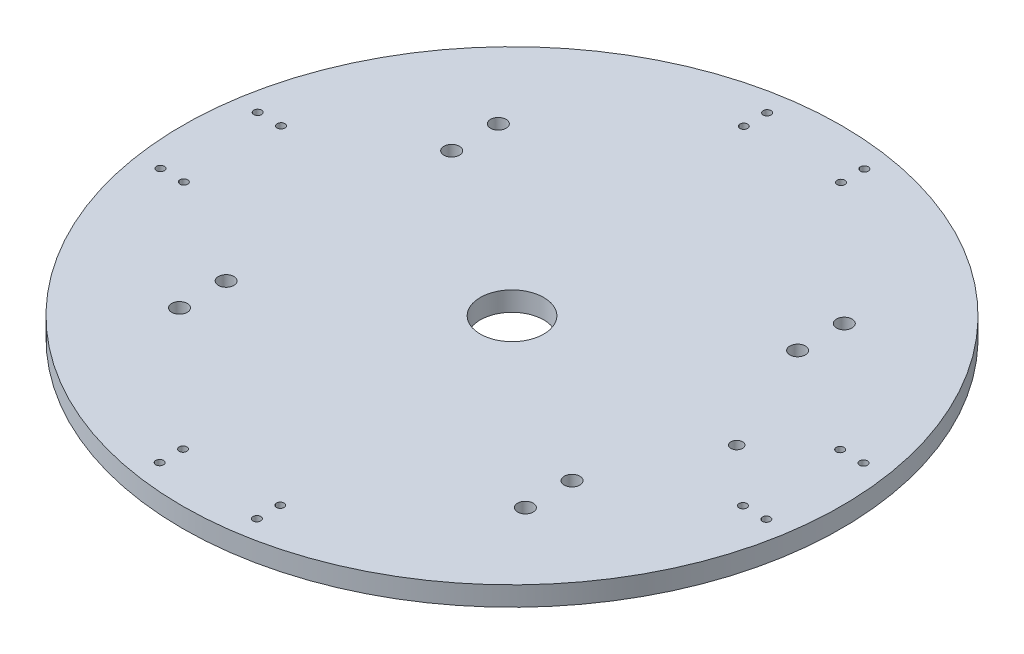
SolidWorks part; units mm, degrees
material "ABS"
ref_plane "Front Plane" through (0, 0, 0) normal (0, 0, 1) x (1, 0, 0)
ref_plane "Top Plane" through (0, 0, 0) normal (0, 1, 0) x (1, 0, 0)
ref_plane "Right Plane" through (0, 0, 0) normal (1, 0, 0) x (0, 0, -1)
sketch "Sketch2" plane through (0, 0, 0) normal (0, 1, 0) x (1, 0, 0)
  line L1 (0, 0) -> (200, 0)
  line L2 (0, 0) -> (0, 200)
  line L3 (0, 200) -> (200, 200)
  line L4 (200, 0) -> (200, 200)
  dimension "D1" = 200
  dimension "D2" = 200
extrude "Boss-Extrude2" add sketch "Sketch2" along normal blind 60
sketch "Sketch3" plane through (0, 0, 0) normal (0, 0, 1) x (1, 0, 0)
  line L0 (40, 60) -> (80.9808, 130.9808)
  line L1 (0, 60) -> (200, 60) construction
  line L2 (160, 60) -> (119.0192, 130.9808)
  line L3 (40, 60) -> (160, 60)
  arc A0 (80.9808, 130.9808) -> (119.0192, 130.9808) centre (100, 120) cw
  dimension "D1" = 120
  dimension "D2" = 40
  dimension "D3" = 60
  dimension "D4" = 60
  dimension "D5" = 60
extrude "Boss-Extrude3" add sketch "Sketch3" against normal blind 41 from offset 38 offset against normal yes
sketch "Sketch4" plane through (0, 0, -79) normal (0, 0, -1) x (-1, 0, 0)
  line L0 (-106.5, 103) -> (-93.5, 103)
  line L1 (-106.5, 107) -> (-93.5, 107)
  line L2 (-103.5, 107) -> (-102, 122)
  line L3 (-96.5, 107) -> (-98, 122)
  line L4 (-106.5, 105) -> (-93.5, 105) construction
  line L5 (-103, 103) -> (-102, 91)
  line L6 (-97, 103) -> (-98, 91)
  line L8 (-40, 60) -> (-160, 60) construction
  arc A0 (-106.5, 103) -> (-106.5, 107) centre (-106.5, 105) cw
  arc A1 (-93.5, 107) -> (-93.5, 103) centre (-93.5, 105) cw
  arc A2 (-102, 122) -> (-98, 122) centre (-100, 122) cw
  arc A3 (-102, 91) -> (-98, 91) centre (-100, 91) ccw
  point P6 (-108.5, 105)
  point P7 (-91.5, 105)
  point P12 (-100, 107)
  point P14 (-100, 124)
  point P19 (-100, 103)
  point P21 (-100, 89)
  point P30 (-100, 105)
  dimension "D3" = 2
  dimension "D1" = 17
  dimension "D2" = 7
  dimension "D4" = 3.5
  dimension "D5" = 17
  dimension "D6" = 6
  dimension "D7" = 3
  dimension "D8" = 14
  dimension "D9" = 4
  dimension "D10" = 4
  dimension "D11" = 60
  dimension "D12" = 45
sketch "Sketch5" plane through (0, 0, 0) normal (0, -1, 0) x (1, 0, 0)
  line L0 (0, 0) -> (200, 0) construction
  line L1 (10, -10) -> (190, -10)
  line L2 (10, -10) -> (10, -190)
  line L3 (10, -190) -> (190, -190)
  line L4 (190, -10) -> (190, -190)
  line L5 (0, -200) -> (0, 0) construction
  line L6 (200, -200) -> (0, -200) construction
  line L7 (200, 0) -> (200, -200) construction
  dimension "D1" = 10
  dimension "D2" = 10
  dimension "D3" = 10
  dimension "D4" = 10
extrude "Cut-Extrude2" cut sketch "Sketch5" against normal blind 50
sketch "Sketch7" plane through (0, 0, -200) normal (0, 0, -1) x (-1, 0, 0)
  line L0 (-160, 60) -> (-40, 60)
  line L1 (-40, 60) -> (-80.9808, 130.9808)
  line L2 (-160, 60) -> (-119.0192, 130.9808)
  arc A0 (-119.0192, 130.9808) -> (-80.9808, 130.9808) centre (-100, 120) cw
extrude "Boss-Extrude4" add sketch "Sketch7" against normal blind 30 from offset 51.2 offset against normal yes
sketch "Sketch8" plane through (0, 0, -38) normal (0, 0, 1) x (1, 0, 0)
  line L9 (48.6603, 65) -> (151.3397, 65)
  line L10 (85.3109, 128.4808) -> (48.6603, 65)
  line L11 (151.3397, 65) -> (114.6891, 128.4808)
  line L12 (48.6603, 65) -> (151.3397, 65)
  line L13 (85.3109, 128.4808) -> (48.6603, 65)
  line L16 (151.3397, 65) -> (114.6891, 128.4808)
  arc A6 (114.6891, 128.4808) -> (85.3109, 128.4808) centre (100, 120) ccw
  arc A7 (114.6891, 128.4808) -> (85.3109, 128.4808) centre (100, 120) ccw
  dimension "D1" = 5
extrude "Cut-Extrude3" cut sketch "Sketch8" against normal blind 35
sketch "Sketch9" plane through (0, 0, -118.8) normal (0, 0, 1) x (1, 0, 0)
  line L0 (200, 60) -> (0, 60) construction
  line L1 (95, 105) -> (95, 149.6169)
  line L2 (105, 105) -> (105, 149.6169)
  line L3 (95, 149.6169) -> (105, 149.6169)
  circle A0 centre (100, 105) radius 5
  arc M3 (119.0192, 130.9808) -> (80.9808, 130.9808) centre (100, 120) ccw
  dimension "D1" = 10
  dimension "D2" = 60
  dimension "D3" = 45
extrude "Cut-Extrude4" cut sketch "Sketch9" against normal blind 10 contours A0 L2 L1 M3 | A0 region at (100, 125.3301, -118.8) region at (100, 105, -118.8)
sketch "Sketch10" plane through (0, 0, -148.8) normal (0, 0, -1) x (-1, 0, 0)
  line L12 (-200, 60) -> (0, 60) construction
  line L13 (-119.0192, 130.9808) -> (-160, 60) construction
  line L14 (-40, 60) -> (-80.9808, 130.9808) construction
  line L15 (-160, 60) -> (-40, 60)
  line L16 (-119.0192, 130.9808) -> (-160, 60)
  line L17 (-40, 60) -> (-80.9808, 130.9808)
  line L18 (-95, 105) -> (-95, 149.6169) construction
  line L19 (-105, 105) -> (-105, 149.6169) construction
  line L20 (-95, 105) -> (-95, 141.3848)
  line L21 (-105, 105) -> (-105, 141.3848)
  line L22 (-151.3397, 65) -> (-48.6603, 65)
  line L23 (-48.6603, 65) -> (-85.3109, 128.4808)
  line L24 (-90, 105) -> (-90, 133.7001)
  line L25 (-110, 105) -> (-110, 133.7001)
  line L26 (-114.6891, 128.4808) -> (-151.3397, 65)
  arc A1 (-80.9808, 130.9808) -> (-119.0192, 130.9808) centre (-100, 120) ccw construction
  arc A2 (-80.9808, 130.9808) -> (-95, 141.3848) centre (-100, 120) ccw
  circle A3 centre (-100, 105) radius 5 construction
  arc A4 (-105, 105) -> (-95, 105) centre (-100, 105) ccw
  arc A5 (-105, 141.3848) -> (-119.0192, 130.9808) centre (-100, 120) ccw
  arc A6 (-85.3109, 128.4808) -> (-90, 133.7001) centre (-100, 120) ccw
  arc A7 (-110, 105) -> (-90, 105) centre (-100, 105) ccw
  arc A8 (-110, 133.7001) -> (-114.6891, 128.4808) centre (-100, 120) ccw
  point P14 (-105, 141.3848)
  point P15 (-95, 141.3848)
  dimension "D1" = 5
extrude "Cut-Extrude6" cut sketch "Sketch10" against normal blind 26 contours L25 A8 L26 L22 L23 A6 L24 A7 region at (100, 87.3602, -148.8)
sketch "Sketch11" plane through (0, 60, 0) normal (0, 1, 0) x (1, 0, 0)
  line L1 (40, 118.8) -> (160, 118.8)
  line L2 (40, 118.8) -> (40, 108.8)
  line L3 (40, 108.8) -> (160, 108.8)
  line L4 (160, 118.8) -> (160, 108.8)
  dimension "D1" = 120
  dimension "D2" = 10
extrude "Cut-Extrude7" cut sketch "Sketch11" against normal blind 26
sketch "Sketch12" plane through (200, 0, 0) normal (1, 0, 0) x (0, 0, -1)
  line L0 (0, 60) -> (200, 60) construction
  line L1 (10, 0) -> (190, 0)
  line L2 (10, 0) -> (10, 50)
  line L3 (10, 50) -> (190, 50)
  line L4 (190, 0) -> (190, 50)
  dimension "D1" = 10
  dimension "D2" = 10
extrude "Cut-Extrude8" cut sketch "Sketch12" against normal blind 200
sketch "Sketch13" plane through (0, 0, 0) normal (0, 0, 1) x (1, 0, 0)
  line L0 (0, 0) -> (200, 0) construction
  line L1 (10, 0) -> (190, 0)
  line L2 (10, 0) -> (10, 50)
  line L3 (10, 50) -> (190, 50)
  line L4 (190, 0) -> (190, 50)
  line L5 (200, 60) -> (200, 0) construction
  line L6 (0, 60) -> (200, 60) construction
  dimension "D1" = 10
  dimension "D2" = 10
  dimension "D3" = 10
extrude "Cut-Extrude9" cut sketch "Sketch13" against normal blind 200
sketch "Sketch15" plane through (0, 0, -73) normal (0, 0, 1) x (1, 0, 0)
  line L0 (106.5, 105) -> (93.5, 105) construction
  line L2 (90.1, 74.4) -> (109.9, 74.4)
  line L3 (90.1, 74.4) -> (90.1, 115)
  line L4 (90.1, 115) -> (109.9, 115)
  line L5 (109.9, 74.4) -> (109.9, 115)
  circle A0 centre (100, 105) radius 4.0162
  point P8 (100, 74.4)
  dimension "D1" = 40.6
  dimension "D2" = 19.8
  dimension "D3" = 10
extrude "Cut-Extrude11" cut sketch "Sketch15" against normal blind 10 contours A0 | L2 L5 L4 L3 A0 region at (100, 94.0071, -73) region at (100, 105, -73)
sketch "Sketch16" plane through (0, 0, -73) normal (0, 0, 1) x (1, 0, 0)
  line L3 (109.9, 74.4) -> (109.9, 115) construction
  line L4 (90.1, 74.4) -> (109.9, 74.4) construction
  line L5 (90.1, 74.4) -> (90.1, 115) construction
  line L6 (88.1, 115) -> (88.1, 72.4)
  line L7 (88.1, 72.4) -> (111.9, 72.4)
  line L8 (111.9, 72.4) -> (111.9, 115)
  line L9 (88.1, 115) -> (88.1, 72.4)
  line L10 (88.1, 72.4) -> (111.9, 72.4)
  line L11 (111.9, 72.4) -> (111.9, 115)
  line L12 (109.9, 74.4) -> (109.9, 115)
  line L13 (90.1, 74.4) -> (109.9, 74.4)
  line L14 (90.1, 74.4) -> (90.1, 115)
  line L15 (88.1, 115) -> (90.1, 115)
  line L16 (109.9, 115) -> (111.9, 115)
  dimension "D1" = 2
extrude "Boss-Extrude5" add sketch "Sketch16" along normal blind 26
sketch "Sketch20" plane through (0, 0, -79) normal (0, 0, -1) x (-1, 0, 0)
  line L0 (-90.1, 74.4) -> (-90.1, 115) construction
  line L1 (-109.9, 115) -> (-90.1, 115)
  line L2 (-109.9, 115) -> (-109.9, 122)
  line L3 (-109.9, 122) -> (-90.1, 122)
  line L4 (-90.1, 115) -> (-90.1, 122)
  line L6 (-109.9, 74.4) -> (-90.1, 74.4)
  line L7 (-109.9, 74.4) -> (-109.9, 67.4)
  line L8 (-109.9, 67.4) -> (-90.1, 67.4)
  line L9 (-90.1, 74.4) -> (-90.1, 67.4)
  dimension "D1" = 7
  dimension "D2" = 7
extrude "Cut-Extrude14" cut sketch "Sketch20" against normal blind 8.2
sketch "Sketch22" plane through (4.0192, -2.3205, 0) normal (-0.866, 0.5, 0) x (0, 0, 1)
  line L4 (-144.8, 81.5368) -> (-122.8, 81.5368)
  line L5 (-38, 71.9615) -> (-38, 131.9615) construction
  line L6 (-75, 151.923) -> (-42, 151.923)
  line L7 (-75, 151.923) -> (-75, 81.566)
  line L8 (-122.8, 75.9615) -> (-122.8, 149.923)
  line L9 (-144.8, 75.9615) -> (-122.8, 75.9615)
  line L10 (-144.8, 149.923) -> (-144.8, 75.9615)
  line L11 (-122.8, 149.923) -> (-144.8, 149.923)
  line L12 (-122.8, 81.5368) -> (-122.8, 149.923)
  line L14 (-144.8, 149.923) -> (-144.8, 81.5368)
  line L15 (-122.8, 149.923) -> (-144.8, 149.923)
  line L16 (-75, 81.566) -> (-42, 81.566)
  line L17 (-42, 151.923) -> (-42, 81.566)
  line L18 (-79, 153.923) -> (-79, 71.9615) construction
  line L19 (-79, 153.923) -> (-38, 153.923) construction
  dimension "D2" = 4
  dimension "D3" = 4
  dimension "D4" = 2
  dimension "D1" = 4
extrude "Cut-Extrude16" cut sketch "Sketch22" against normal blind 6
sketch "Sketch23" plane through (0, 0, -38) normal (0, 0, 1) x (1, 0, 0)
  line L3 (43.4641, 62) -> (42.3094, 60)
  line L4 (0, 60) -> (200, 60) construction
  line L6 (156.5359, 62) -> (117.2872, 129.9808)
  line L7 (43.4641, 62) -> (156.5359, 62)
  line L8 (82.7128, 129.9808) -> (43.4641, 62)
  line L9 (156.5359, 62) -> (117.2872, 129.9808)
  line L11 (82.7128, 129.9808) -> (43.4641, 62)
  line L12 (40, 60) -> (160, 60) construction
  line L13 (157.6906, 60) -> (156.5359, 62)
  line L14 (42.3094, 60) -> (36.9518, 60)
  line L15 (36.9518, 60) -> (100, 183.6882)
  line L16 (100, 183.6882) -> (162.6048, 60)
  line L17 (162.6048, 60) -> (157.6906, 60)
  arc A2 (117.2872, 129.9808) -> (82.7128, 129.9808) centre (100, 120) ccw
  arc A3 (117.2872, 129.9808) -> (82.7128, 129.9808) centre (100, 120) ccw
  dimension "D1" = 2
extrude "Cut-Extrude17" cut sketch "Sketch23" against normal blind 150
sketch "Sketch24" plane through (0, 0, -200) normal (0, 0, -1) x (-1, 0, 0)
  line L0 (-200, 0) -> (-190, 0) construction
  line L1 (-195, 0) -> (-5, 0)
  line L2 (-195, 0) -> (-195, 55)
  line L3 (-195, 55) -> (-5, 55)
  line L4 (-5, 0) -> (-5, 55)
  line L5 (-10, 0) -> (0, 0) construction
  line L9 (-190, 50) -> (-10, 50) construction
  dimension "D1" = 5
extrude "Cut-Extrude18" cut sketch "Sketch24" against normal blind 200
sketch "Sketch38" plane through (0, 0, -148.8) normal (0, 0, -1) x (-1, 0, 0)
  line L3 (-110, 133.7001) -> (-107, 135.7639)
  line L4 (-90, 133.7001) -> (-93, 135.7639)
  line L5 (-90, 105) -> (-90, 133.7001) construction
  line L6 (-110, 105) -> (-110, 133.7001) construction
  line L7 (-90, 105) -> (-90, 133.7001)
  line L8 (-110, 105) -> (-110, 133.7001)
  line L11 (-107, 105) -> (-107, 135.7639)
  line L12 (-93, 105) -> (-93, 135.7639)
  arc A5 (-110, 105) -> (-90, 105) centre (-100, 105) ccw construction
  arc A6 (-110, 105) -> (-90, 105) centre (-100, 105) ccw
  arc A7 (-107, 105) -> (-93, 105) centre (-100, 105) ccw
sketch "Sketch41" plane through (0, 60, 0) normal (0, 1, 0) x (1, 0, 0)
  line L1 (0, 200) -> (200, 200)
  line L2 (0, 200) -> (0, 0)
  line L3 (0, 0) -> (200, 0)
  line L4 (200, 200) -> (200, 0)
  line L5 (42.3094, 148.8) -> (157.6906, 148.8)
  line L6 (42.3094, 148.8) -> (42.3094, 38)
  line L7 (42.3094, 38) -> (157.6906, 38)
  line L8 (157.6906, 148.8) -> (157.6906, 38)
extrude "Cut-Extrude25" cut sketch "Sketch41" against normal blind 100
extrude "Cut-Extrude26" cut sketch "Sketch38" against normal blind 26
sketch "Sketch43" plane through (0, 55, 0) normal (0, -1, 0) x (1, 0, 0)
  line L1 (157.6906, -148.8) -> (42.3094, -148.8) construction
  line L2 (42.3094, -38) -> (157.6906, -38) construction
  circle A0 centre (100, -98.8) radius 85
  point P7 (100, -38)
  dimension "D2" = 170
  dimension "D1" = 50
extrude "Boss-Extrude9" add sketch "Sketch43" against normal blind 5
sketch "Sketch45" plane through (0, 0, -38) normal (0, 0, 1) x (1, 0, 0)
  line L0 (42.3094, 60) -> (82.7128, 129.9808) construction
  line L1 (42.3094, 60) -> (82.7128, 129.9808)
  line L2 (157.6906, 60) -> (42.3094, 60) construction
  line L3 (117.2872, 129.9808) -> (157.6906, 60) construction
  line L4 (157.6906, 60) -> (42.3094, 60)
  line L5 (117.2872, 129.9808) -> (157.6906, 60)
  line L6 (151.3397, 65) -> (114.6891, 128.4808) construction
  line L7 (48.6603, 65) -> (151.3397, 65) construction
  line L8 (85.3109, 128.4808) -> (48.6603, 65) construction
  line L9 (151.3397, 65) -> (114.6891, 128.4808)
  line L10 (48.6603, 65) -> (151.3397, 65)
  line L11 (85.3109, 128.4808) -> (48.6603, 65)
  arc A0 (117.2872, 129.9808) -> (82.7128, 129.9808) centre (100, 120) ccw construction
  arc A1 (117.2872, 129.9808) -> (82.7128, 129.9808) centre (100, 120) ccw
  arc A2 (114.6891, 128.4808) -> (85.3109, 128.4808) centre (100, 120) ccw construction
  arc A3 (114.6891, 128.4808) -> (85.3109, 128.4808) centre (100, 120) ccw
extrude "Cut-Extrude27" cut sketch "Sketch45" against normal blind 11
sketch "Sketch46" plane through (0, 0, -49) normal (0, 0, 1) x (1, 0, 0)
  line L0 (81.7128, 128.2487) -> (46.5343, 67.3177)
  line L1 (81.7128, 128.2487) -> (84.2728, 126.7707)
  line L2 (46.5343, 67.3177) -> (49.0943, 65.8397)
  line L3 (84.2728, 126.7707) -> (49.0943, 65.8397)
extrude "Boss-Extrude10" add sketch "Sketch46" against normal blind 4
sketch "Sketch47" plane through (0, 0, -73) normal (0, 0, 1) x (1, 0, 0)
  line L0 (49.1324, 65.8177) -> (50.5487, 65)
  line L1 (48.6603, 65) -> (151.3397, 65) construction
  line L2 (50.5487, 65) -> (48.6603, 65)
  line L3 (48.6603, 65) -> (49.1324, 65.8177)
extrude "Boss-Extrude11" add sketch "Sketch47" along normal blind 24
sketch "Sketch48" plane through (0, 0, -122.8) normal (0, 0, -1) x (-1, 0, 0)
  line L0 (-49.1177, 65.7924) -> (-50.4902, 65)
  line L1 (-151.3397, 65) -> (-48.6603, 65) construction
  line L2 (-50.4902, 65) -> (-48.6603, 65)
  line L3 (-48.6603, 65) -> (-49.1177, 65.7924)
extrude "Boss-Extrude12" add sketch "Sketch48" along normal blind 26
sketch "Sketch49" plane through (0, 0, -75) normal (0, 0, 1) x (1, 0, 0)
  line L0 (49.9984, 65.3177) -> (49.0943, 65.8397)
  line L1 (49.9984, 65.3177) -> (85.1769, 126.2487)
  line L2 (49.0943, 65.8397) -> (84.2728, 126.7707)
  line L3 (85.1769, 126.2487) -> (84.2728, 126.7707)
  line L4 (85.1769, 126.2487) -> (84.3109, 126.7487) construction
  point P8 (84.7249, 126.5097)
extrude "Boss-Extrude14" add sketch "Sketch49" along normal blind 4
sketch "Sketch52" plane through (0, 0, -148.8) normal (0, 0, -1) x (-1, 0, 0)
  line L0 (-93, 135.7639) -> (-93, 105) construction
  line L1 (-107, 105) -> (-107, 135.7639) construction
  line L2 (-93, 135.7639) -> (-93, 105)
  line L3 (-107, 105) -> (-107, 135.7639)
  arc A0 (-107, 105) -> (-93, 105) centre (-100, 105) ccw construction
  arc A1 (-107, 105) -> (-93, 105) centre (-100, 105) ccw
  arc A2 (-107, 135.7639) -> (-93, 135.7639) centre (-100, 120) cw
  arc A3 (-82.7128, 129.9808) -> (-117.2872, 129.9808) centre (-100, 120) ccw construction
extrude "Cut-Extrude29" cut sketch "Sketch52" against normal blind 18
sketch "Sketch53" plane through (0, 0, -71) normal (0, 0, 1) x (1, 0, 0)
  line L0 (85.1769, 126.2487) -> (84.2728, 126.7707)
  line L1 (85.1769, 126.2487) -> (49.9948, 65.3116)
  line L2 (84.2728, 126.7707) -> (49.0907, 65.8336)
  line L3 (49.9948, 65.3116) -> (49.0907, 65.8336)
extrude "Cut-Extrude30" cut sketch "Sketch53" against normal blind 2
sketch "Sketch54" plane through (0, 0, -73) normal (0, 0, 1) x (1, 0, 0)
  line L0 (151.3397, 65) -> (114.6891, 128.4808) construction
  line L1 (84.2728, 126.7707) -> (49.0943, 65.8397) construction
  line L2 (50.5487, 65) -> (151.3397, 65) construction
  line L3 (49.0907, 65.8336) -> (49.9948, 65.3116) construction
  line L4 (151.3397, 65) -> (114.6891, 128.4808)
  line L5 (84.2728, 126.7707) -> (49.0943, 65.8397)
  line L6 (50.5487, 65) -> (151.3397, 65)
  line L7 (49.0907, 65.8336) -> (49.9948, 65.3116)
  line L8 (84.2728, 126.7707) -> (85.3109, 128.4808)
  line L9 (90.1, 67.4) -> (90.1, 72.4)
  line L10 (88.1, 72.4) -> (111.9, 72.4) construction
  line L11 (90.1, 72.4) -> (90.1, 67.4) construction
  line L12 (90.1, 72.4) -> (88.1, 72.4)
  line L13 (88.1, 72.4) -> (88.1, 115)
  line L14 (88.1, 115) -> (90.1, 115)
  line L15 (90.1, 115) -> (90.1, 122)
  line L16 (90.1, 122) -> (109.9, 122)
  line L17 (109.9, 122) -> (109.9, 115)
  line L18 (109.9, 115) -> (111.9, 115)
  line L19 (111.9, 115) -> (111.9, 72.4)
  line L20 (111.9, 72.4) -> (109.9, 72.4)
  line L21 (109.9, 72.4) -> (111.9, 72.4) construction
  line L22 (109.9, 72.4) -> (109.9, 67.4)
  line L23 (109.9, 67.4) -> (90.1, 67.4)
  arc A0 (114.6891, 128.4808) -> (85.3109, 128.4808) centre (100, 120) ccw construction
  arc A1 (114.6891, 128.4808) -> (85.3109, 128.4808) centre (100, 120) ccw
  line M13 (49.9948, 65.3116) -> (49.9984, 65.3177)
  line M14 (49.9984, 65.3177) -> (50.5487, 65)
  line M15 (50.5487, 65) -> (151.3397, 65)
  line M16 (151.3397, 65) -> (114.6891, 128.4808)
  arc M17 (114.6891, 128.4808) -> (85.3109, 128.4808) centre (100, 120) ccw
  line M18 (85.3109, 128.4808) -> (84.3109, 126.7487)
  line M19 (84.3109, 126.7487) -> (84.2728, 126.7707)
  line M20 (84.2728, 126.7707) -> (49.0943, 65.8397)
  line M21 (49.0943, 65.8397) -> (49.0907, 65.8336)
  line M22 (49.0907, 65.8336) -> (49.9948, 65.3116)
  line M23 (109.9, 122) -> (109.9, 115)
  line M24 (109.9, 115) -> (111.9, 115)
  line M25 (111.9, 115) -> (111.9, 72.4)
  line M26 (111.9, 72.4) -> (109.9, 72.4)
  line M27 (109.9, 72.4) -> (109.9, 67.4)
  line M28 (109.9, 67.4) -> (90.1, 67.4)
  line M29 (90.1, 67.4) -> (90.1, 72.4)
  line M30 (90.1, 72.4) -> (88.1, 72.4)
  line M31 (88.1, 72.4) -> (88.1, 115)
  line M32 (88.1, 115) -> (90.1, 115)
  line M33 (90.1, 115) -> (90.1, 122)
  line M34 (90.1, 122) -> (109.9, 122)
extrude "Cut-Extrude31" cut sketch "Sketch54" against normal blind 2 contours M22 M13 M14 M15 M16 M17 M18 M19 M20 M21 M34 M23 M24 M25 M26 M27 M28 M29 M30 M31 M32 M33 region at (100.9442, 66.2503, -73)
sketch "Sketch55" plane through (0, 0, -75) normal (0, 0, 1) x (1, 0, 0)
  line L0 (90.1, 67.4) -> (109.9, 67.4)
  line L1 (90.1, 67.4) -> (90.1, 64.9898)
  line L2 (109.9, 67.4) -> (109.9, 64.9898)
  line L3 (90.1, 64.9898) -> (109.9, 64.9898)
extrude "Boss-Extrude16" add sketch "Sketch55" along normal blind 4
sketch "Sketch56" plane through (144.2487, 83.282, 0) normal (0.866, 0.5, 0) x (0, 0, -1)
  line L0 (79, -26.8838) -> (49, -26.8838) construction
  line L1 (53, 51.923) -> (75, 51.923)
  line L2 (53, 51.923) -> (53, -18.4338)
  line L3 (53, -18.4338) -> (75, -18.4338)
  line L4 (75, 51.923) -> (75, -18.4338)
  line L5 (122.8, 51.923) -> (144.8, 51.923)
  line L6 (122.8, 51.923) -> (122.8, -18.4338)
  line L7 (122.8, -18.4338) -> (144.8, -18.4338)
  line L8 (144.8, 51.923) -> (144.8, -18.4338)
  line L9 (79, -26.8838) -> (79, 53.923) construction
  line L10 (49, -26.8838) -> (49, 53.923) construction
  line L11 (79, 53.923) -> (49, 53.923) construction
  line L12 (118.8, 53.923) -> (118.8, -26.8838) construction
  line L13 (148.8, 53.923) -> (148.8, -26.8838) construction
  dimension "D1" = 8.45
  dimension "D2" = 4
  dimension "D3" = 4
  dimension "D4" = 2
  dimension "D5" = 4
  dimension "D6" = 4
extrude "Cut-Extrude32" cut sketch "Sketch56" against normal blind 4
sketch "Sketch57" plane through (0, 0, -75) normal (0, 0, 1) x (1, 0, 0)
  line L0 (150.8675, 65.8179) -> (149.4509, 65)
  line L1 (50.5487, 65) -> (151.3397, 65) construction
  line L2 (149.4509, 65) -> (151.3397, 65)
  line L3 (151.3397, 65) -> (150.8675, 65.8179)
extrude "Boss-Extrude17" add sketch "Sketch57" along normal blind 26
sketch "Sketch58" plane through (0, 0, -122.8) normal (0, 0, -1) x (-1, 0, 0)
  line L0 (-150.8675, 65.8179) -> (-151.3397, 65)
  line L1 (-150.8675, 65.8179) -> (-149.4509, 65)
  line L2 (-151.3397, 65) -> (-50.4902, 65) construction
  line L3 (-149.4509, 65) -> (-151.3397, 65)
extrude "Boss-Extrude18" add sketch "Sketch58" along normal blind 26
sketch "Sketch59" plane through (0, 0, 0) normal (1, 0, 0) x (0, 0, -1)
  line L0 (81.4, 60) -> (94.15, 72.75)
  line L1 (183.8, 60) -> (13.8, 60) construction
  line L2 (116.4, 60) -> (103.65, 72.75)
  line L3 (79, 60) -> (79, 129.9808) construction
  line L4 (81.4, 60) -> (116.4, 60)
  line L5 (13.8, 57.5) -> (38.5801, 57.5) construction
  line L6 (13.8, 60) -> (13.8, 55) construction
  line L7 (81.4, 55) -> (116.4, 55)
  line L8 (116.4, 55) -> (103.65, 42.25)
  line L9 (81.4, 55) -> (94.15, 42.25)
  arc A0 (94.15, 72.75) -> (103.65, 72.75) centre (98.9, 68) cw
  arc A1 (94.15, 42.25) -> (103.65, 42.25) centre (98.9, 47) ccw
  dimension "D1" = 35
  dimension "D2" = 19.9
  dimension "D3" = 17.5
  dimension "D4" = 45
  dimension "D5" = 8
extrude "Boss-Extrude19" add sketch "Sketch59" along normal blind 10 from offset 170
sketch "Sketch60" plane through (180, 0, 0) normal (1, 0, 0) x (0, 0, -1)
  line L1 (81.4, 60) -> (116.4, 60) construction
  line L2 (13.8, 57.5) -> (18.7566, 57.5) construction
  line L3 (13.8, 60) -> (13.8, 55) construction
  circle A0 centre (98.9, 70) radius 2.45
  arc A1 (103.65, 72.75) -> (94.15, 72.75) centre (98.9, 68) ccw construction
  circle A2 centre (98.9, 45) radius 2.45
  point P6 (98.9, 74.7175)
  dimension "D1" = 4.9
  dimension "D2" = 10
extrude "Boss-Extrude20" add sketch "Sketch60" along normal blind 9
fillet "Fillet1" radius 0.3 2 edges at (189, 70, -101.35) (189, 45, -96.45)
sketch "Sketch61" plane through (189, 0, 0) normal (1, 0, 0) x (0, 0, -1)
  line L0 (13.8, 57.5) -> (19.9203, 57.5) construction
  line L1 (13.8, 60) -> (13.8, 55) construction
  circle A0 centre (98.9, 70) radius 2.375
  circle A1 centre (98.9, 70) radius 2.45
  circle A2 centre (98.9, 45) radius 2.45
  circle A3 centre (98.9, 45) radius 2.375
  dimension "D1" = 4.75
  dimension "D2" = 4.9
extrude "Cut-Extrude33" cut sketch "Sketch61" against normal blind 5.2 from offset 1 offset against normal yes
fillet "Fillet2" radius 2 2 edges at (180, 70, -96.45) (180, 45, -96.45)
sketch "Sketch62" plane through (170, 0, 0) normal (-1, 0, 0) x (0, 0, 1)
  line L0 (-81.4, 55) -> (-94.15, 42.25) construction
  line L1 (-116.4, 55) -> (-81.4, 55) construction
  line L2 (-103.65, 42.25) -> (-116.4, 55) construction
  line L3 (-81.4, 55) -> (-94.15, 42.25)
  line L4 (-116.4, 55) -> (-81.4, 55)
  line L5 (-103.65, 42.25) -> (-116.4, 55)
  arc A0 (-103.65, 42.25) -> (-94.15, 42.25) centre (-98.9, 47) ccw construction
  arc A1 (-103.65, 42.25) -> (-94.15, 42.25) centre (-98.9, 47) ccw
extrude "Boss-Extrude21" add sketch "Sketch62" along normal blind 10 from offset 140
sketch "Sketch63" plane through (20, 0, 0) normal (-1, 0, 0) x (0, 0, 1)
  circle A0 centre (-98.9, 45) radius 2.45 construction
  circle A1 centre (-98.9, 45) radius 2.45
extrude "Boss-Extrude22" add sketch "Sketch63" along normal blind 9
fillet "Fillet3" radius 0.3 1 edges at (11, 45, -96.45)
fillet "Fillet4" radius 2 1 edges at (20, 45, -96.45)
sketch "Sketch64" plane through (11, 0, 0) normal (-1, 0, 0) x (0, 0, 1)
  circle A0 centre (-98.9, 45) radius 2.375 construction
  circle A1 centre (-98.9, 45) radius 2.375
  circle A2 centre (-98.9, 45) radius 2.45 construction
  circle A3 centre (-98.9, 45) radius 2.45
extrude "Cut-Extrude34" cut sketch "Sketch64" against normal blind 5.2 from offset 1 contours A3 A1 region at (11, 45, -101.2807) offset against normal yes
sketch "Sketch67" plane through (0, 60, 0) normal (0, 1, 0) x (1, 0, 0)
  circle A0 centre (100, 98.8) radius 95.1684
  circle A1 centre (100, 98.8) radius 85 construction
  circle A2 centre (100, 98.8) radius 84.75
  dimension "D1" = 169.5
extrude "Cut-Extrude36" cut sketch "Sketch67" against normal blind 5
sketch "Sketch68" plane through (0, 65, 0) normal (0, 1, 0) x (1, 0, 0)
  line L2 (50.4902, 148.8) -> (50.4902, 122.8) construction
  line L3 (149.4509, 148.8) -> (149.4509, 122.8) construction
  line L4 (153.4656, 144.8) -> (118.2872, 144.8) construction
  line L5 (149.4509, 122.8) -> (50.4902, 122.8) construction
  line L14 (30, 81.4) -> (30, 116.4) construction
  line L15 (30, 94.15) -> (30, 81.4) construction
  line L16 (20, 116.4) -> (20, 103.65) construction
  line L17 (20, 94.15) -> (20, 81.4) construction
  line L18 (20, 81.4) -> (30, 81.4) construction
  line L19 (20, 116.4) -> (30, 116.4) construction
  line L24 (100, 98.8) -> (118.0034, 98.8) construction
  circle A0 centre (55.4902, 139.8) radius 2.0133
  circle A1 centre (55.4902, 127.8) radius 2.0753
  circle A2 centre (144.4509, 139.8) radius 1.8562
  circle A3 centre (144.4509, 127.8) radius 2.0259
  circle A12 centre (22, 86.4) radius 0.6969
  circle A13 centre (28, 86.4) radius 1.4595
  circle A14 centre (28, 111.4) radius 1.4464
  circle A15 centre (22, 111.4) radius 0.9285
  circle A16 centre (87.6, 176.8) radius 0.6969
  circle A17 centre (87.6, 170.8) radius 1.4595
  circle A18 centre (112.6, 170.8) radius 1.4464
  circle A19 centre (112.6, 176.8) radius 0.9285
  circle A20 centre (178, 111.2) radius 0.6969
  circle A21 centre (172, 111.2) radius 1.4595
  circle A22 centre (172, 86.2) radius 1.4464
  circle A23 centre (178, 86.2) radius 0.9285
  circle A24 centre (112.4, 20.8) radius 0.6969
  circle A25 centre (112.4, 26.8) radius 1.4595
  circle A26 centre (87.4, 26.8) radius 1.4464
  circle A27 centre (87.4, 20.8) radius 0.9285
  circle A29 centre (144.4509, 69.8) radius 2.0259
  circle A30 centre (144.4509, 57.8) radius 1.8562
  circle A31 centre (55.4902, 69.8) radius 2.0753
  circle A32 centre (55.4902, 57.8) radius 2.0133
  point P53 (87.6, 176.8)
  point P54 (87.6, 170.8)
  point P75 (112.6, 176.8)
  point P76 (22, 86.4)
  point P77 (28, 86.4)
  point P78 (22, 111.4)
  point P79 (28, 111.4)
  point P80 (112.6, 170.8)
  point P84 (55.4902, 139.8)
  point P85 (55.4902, 127.8)
  point P86 (144.4509, 127.8)
  point P87 (144.4509, 139.8)
  point P97 (178, 111.2)
  point P98 (172, 111.2)
  point P99 (178, 86.2)
  point P100 (172, 86.2)
  point P109 (112.4, 20.8)
  point P110 (112.4, 26.8)
  point P111 (87.4, 20.8)
  point P112 (87.4, 26.8)
  point P113 (100, 98.8)
  dimension "D1" = 5
  dimension "D2" = 5
  dimension "D3" = 5
  dimension "D4" = 5
  dimension "D5" = 5
  dimension "D6" = 5
  dimension "D7" = 5
  dimension "D8" = 5
  dimension "D17" = 4
  dimension "D21" = 2
  dimension "D22" = 2
  dimension "D23" = 2
  dimension "D24" = 2
  dimension "D25" = 5
  dimension "D26" = 5
  dimension "D27" = 5
  dimension "D28" = 5
sketch "Sketch73" plane through (180, 0, 0) normal (1, 0, 0) x (0, 0, -1)
  line L1 (14.05, 60) -> (194.292, 60)
  line L2 (14.05, 60) -> (14.05, 148.8261)
  line L3 (14.05, 148.8261) -> (194.292, 148.8261)
  line L4 (194.292, 60) -> (194.292, 148.8261)
  line L5 (14.05, 55) -> (199.1623, 55)
  line L6 (14.05, 55) -> (14.05, 29.1567)
  line L7 (14.05, 29.1567) -> (199.1623, 29.1567)
  line L8 (199.1623, 55) -> (199.1623, 29.1567)
sketch "Sketch75" plane through (0, 60, 0) normal (0, 1, 0) x (1, 0, 0)
  line L1 (170, 81.4) -> (170, 116.4) construction
  circle A0 centre (157.6906, 98.9) radius 1.5
  point P6 (170, 98.9)
  dimension "D1" = 3
extrude "Cut-Extrude38" cut sketch "Sketch75" against normal blind 300
extrude "Cut-Extrude39" cut sketch "Sketch73" against normal blind 300 and the other way blind 300
sketch "Sketch76" plane through (0, 55, 0) normal (0, -1, 0) x (1, 0, 0)
  circle A0 centre (100, -98.8) radius 8.16
  dimension "D1" = 16.32
extrude "Cut-Extrude40" cut sketch "Sketch76" against normal blind 10
sketch "Sketch80" plane through (0, 60, 0) normal (0, 1, 0) x (1, 0, 0)
  circle A0 centre (112.6, 176.8) radius 0.9285 construction
  circle A1 centre (87.6, 176.8) radius 0.6969 construction
  circle A2 centre (87.6, 170.8) radius 1.4595 construction
  circle A3 centre (112.6, 170.8) radius 1.4464 construction
  circle A4 centre (55.4902, 139.8) radius 2.0133 construction
  circle A5 centre (55.4902, 127.8) radius 2.0753 construction
  circle A6 centre (144.4509, 139.8) radius 1.8562 construction
  circle A7 centre (144.4509, 127.8) radius 2.0259 construction
  circle A8 centre (178, 111.2) radius 0.6969 construction
  circle A9 centre (172, 111.2) radius 1.4595 construction
  circle A10 centre (178, 86.2) radius 0.9285 construction
  circle A11 centre (172, 86.2) radius 1.4464 construction
  circle A12 centre (144.4509, 69.8) radius 2.0259 construction
  circle A13 centre (144.4509, 57.8) radius 1.8562 construction
  circle A14 centre (55.4902, 69.8) radius 2.0753 construction
  circle A15 centre (55.4902, 57.8) radius 2.0133 construction
  circle A16 centre (112.4, 20.8) radius 0.6969 construction
  circle A17 centre (112.4, 26.8) radius 1.4595 construction
  circle A18 centre (87.4, 20.8) radius 0.9285 construction
  circle A19 centre (87.4, 26.8) radius 1.4464 construction
  circle A20 centre (28, 86.4) radius 1.4595 construction
  circle A21 centre (22, 86.4) radius 0.6969 construction
  circle A22 centre (22, 111.4) radius 0.9285 construction
  circle A23 centre (28, 111.4) radius 1.4464 construction
  circle A24 centre (112.6, 176.8) radius 0.9285
  circle A25 centre (87.6, 176.8) radius 0.6969
  circle A26 centre (87.6, 170.8) radius 1.4595
  circle A27 centre (112.6, 170.8) radius 1.4464
  circle A28 centre (55.4902, 139.8) radius 2.0133
  circle A29 centre (55.4902, 127.8) radius 2.0753
  circle A30 centre (144.4509, 139.8) radius 1.8562
  circle A31 centre (144.4509, 127.8) radius 2.0259
  circle A32 centre (178, 111.2) radius 0.6969
  circle A33 centre (172, 111.2) radius 1.4595
  circle A34 centre (178, 86.2) radius 0.9285
  circle A35 centre (172, 86.2) radius 1.4464
  circle A36 centre (144.4509, 69.8) radius 2.0259
  circle A37 centre (144.4509, 57.8) radius 1.8562
  circle A38 centre (55.4902, 69.8) radius 2.0753
  circle A39 centre (55.4902, 57.8) radius 2.0133
  circle A40 centre (112.4, 20.8) radius 0.6969
  circle A41 centre (112.4, 26.8) radius 1.4595
  circle A42 centre (87.4, 20.8) radius 0.9285
  circle A43 centre (87.4, 26.8) radius 1.4464
  circle A44 centre (28, 86.4) radius 1.4595
  circle A45 centre (22, 86.4) radius 0.6969
  circle A46 centre (22, 111.4) radius 0.9285
  circle A47 centre (28, 111.4) radius 1.4464
hole_wizard "Ø2.0mm Dowel Hole4" positions "3DSketch2" profile "Sketch81" hole size "Ø2.0" standard "ANSI Metric" end condition through all
sketch3d "3DSketch2"
  point P0 (28, 60, -111.4)
  point P4 (22, 60, -111.4)
  point P7 (28, 60, -86.4)
  point P10 (22, 60, -86.4)
  point P13 (87.4, 60, -26.8)
  point P16 (87.4, 60, -20.8)
  point P19 (112.4, 60, -20.8)
  point P22 (112.4, 60, -26.8)
  point P25 (172, 60, -86.2)
  point P28 (178, 60, -86.2)
  point P31 (172, 60, -111.2)
  point P34 (178, 60, -111.2)
  point P37 (87.6, 60, -170.8)
  point P40 (112.6, 60, -170.8)
  point P43 (87.6, 60, -176.8)
  point P46 (112.6, 60, -176.8)
sketch "Sketch81" plane through (28, 60, -111.4) normal (1, 0, 0) x (0, 0, 1)
  line L0 (0, 0) -> (0, 5)
  line L1 (0, 5) -> (1, 5)
  line L2 (1, 5) -> (1, 0)
  line L5 (1, 0) -> (0, 0)
  line L11 (0, -6.35) -> (0, 107.95) construction
  dimension "Thru Hole Dia." = 2
  dimension "Thru Hole Depth" = 5
hole_wizard "Ø4.0mm Dowel Hole1" positions "3DSketch3" profile "Sketch82" hole size "Ø4.0" standard "ANSI Metric" end condition through all
sketch3d "3DSketch3"
  point P0 (55.4902, 60, -69.8)
  point P3 (55.4902, 60, -57.8)
  point P6 (144.4509, 60, -57.8)
  point P9 (144.4509, 60, -69.8)
  point P12 (55.4902, 60, -127.8)
  point P15 (55.4902, 60, -139.8)
  point P18 (144.4509, 60, -139.8)
  point P21 (144.4509, 60, -127.8)
sketch "Sketch82" plane through (55.4902, 60, -69.8) normal (1, 0, 0) x (0, 0, 1)
  line L0 (0, 0) -> (0, 5)
  line L1 (0, 5) -> (2, 5)
  line L2 (2, 5) -> (2, 0)
  line L5 (2, 0) -> (0, 0)
  line L11 (0, -6.35) -> (0, 107.95) construction
  dimension "Thru Hole Dia." = 4
  dimension "Thru Hole Depth" = 5
